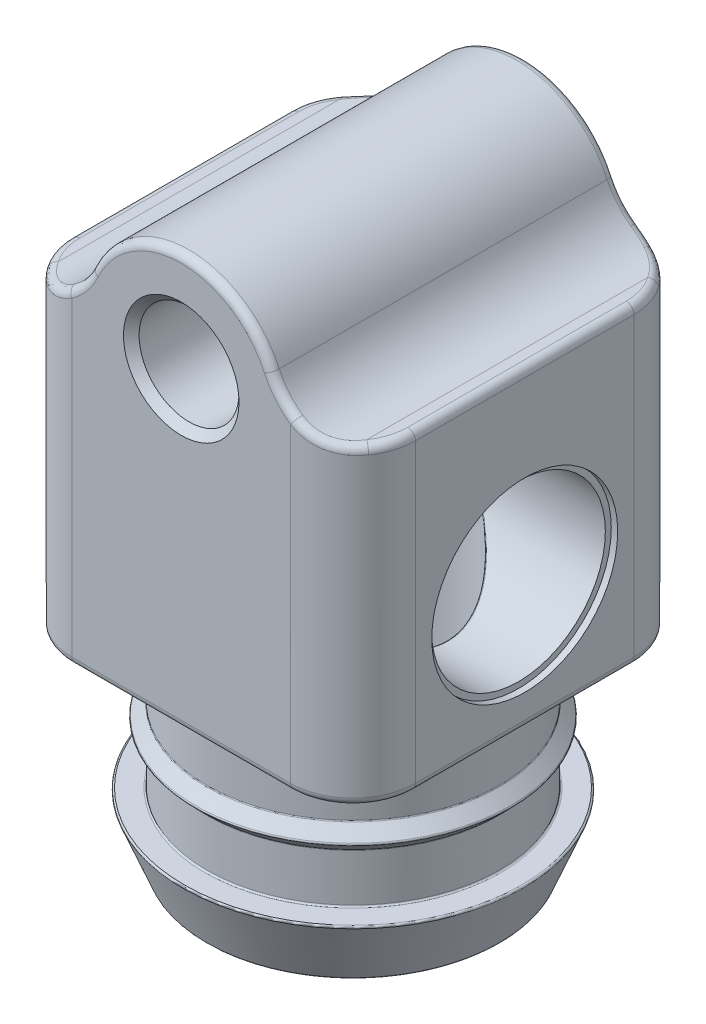
SolidWorks part; units mm, degrees
ref_plane "Front Plane" through (0, 0, 0) normal (0, 0, 1) x (1, 0, 0)
ref_plane "Top Plane" through (0, 0, 0) normal (0, 1, 0) x (1, 0, 0)
ref_plane "Right Plane" through (0, 0, 0) normal (1, 0, 0) x (0, 0, -1)
sketch "Sketch1" plane through (0, 0, 0) normal (0, 0, 1) x (1, 0, 0)
  line L3 (0, 0) -> (0, -20) construction
  line L4 (-11, 0) -> (-6.35, 0)
  line L5 (-11, 0) -> (-11, -20)
  line L6 (-11, -20) -> (11, -20)
  line L7 (11, 0) -> (11, -20)
  line L8 (6.35, 0) -> (11, 0)
  circle A0 centre (0, 0) radius 3.2
  arc A1 (6.35, 0) -> (-6.35, 0) centre (0, 0) ccw
  dimension "D1" = 6.4
  dimension "D2" = 12.7
  dimension "D4" = 22
  dimension "D5" = 20
extrude "Boss-Extrude1" add sketch "Sketch1" along normal mid plane 22
sketch3d "3DSketch1" plane through (0, 0, 0) normal (0, 0, 1) x (1, 0, 0)
  dimension "D1" = 12.7
sketch "Sketch2" plane through (0, 0, 0) normal (0, 0, 1) x (1, 0, 0)
  line L0 (0, 9.544) -> (0, -9.544) construction
  line L1 (0, -20) -> (9.365, -20)
  line L4 (0, -32.7) -> (9.365, -32.7)
  line L10 (0, -32.7) -> (0, -20)
  line L11 (9.365, -32.7) -> (10.9525, -28.7312)
  line L12 (10.9525, -28.7312) -> (9.365, -28.7312)
  line L13 (9.365, -28.7312) -> (9.365, -25.5562)
  line L14 (9.365, -25.5562) -> (10.1588, -24.7625)
  line L15 (10.1588, -24.7625) -> (9.365, -23.9687)
  line L16 (10.1588, -24.7625) -> (9.365, -24.7625) construction
  line L17 (9.365, -23.9687) -> (9.365, -20)
  dimension "D1" = 18.73
  dimension "D2" = 12.7
  dimension "D3" = 1.5875
  dimension "D4" = 3.9688
  dimension "D5" = 0.7937
  dimension "D6" = 7.9375
  dimension "D7" = 20
revolve "Revolve1" add sketch "Sketch2" angle 360 about L0
sketch "Sketch3" plane through (0, -32.7, 0) normal (0, -1, 0) x (1, 0, 0)
  circle A0 centre (0, 0) radius 6
  dimension "D1" = 12
extrude "Cut-Extrude1" cut sketch "Sketch3" against normal blind 27.25 contours A0
hole_wizard "1/4 NPT Tapped Hole1" positions "Sketch4" profile "Sketch5" size "1/4" standard "ANSI Inch" end condition up to next
sketch "Sketch4" plane through (11, 0, 0) normal (1, 0, 0) x (0, 0, -1)
  point P0 (0, -12)
  dimension "D1" = 12
cosmetic thread "Hole Thread1" parameters "D1"=0.4, "D2"=13.1394
sketch "Sketch5" plane through (11, -12, 0) normal (0, 1, 0) x (0, 0, -1)
  line L0 (0, 0) -> (0, 5)
  line L1 (0, 5) -> (5.5626, 5)
  line L2 (-5.9437, 0.4) -> (-5.9557, 0) construction
  line L3 (5.5626, 5) -> (5.5626, 0.4)
  line L4 (5.5626, 0.4) -> (5.9437, 0.4)
  line L5 (5.9437, 0.4) -> (5.9557, 0)
  line L7 (5.9557, 0) -> (0, 0)
  line L8 (0, -6.35) -> (0, 107.95) construction
  line L11 (-5.5626, 0.4) -> (-5.9437, 0.4) construction
  dimension "Thru Tap Drill Dia." = 11.1252
  dimension "Thru Tap Drill Depth" = 5
  dimension "Thread Dia." = 11.9113
  dimension "Thread Angle" = 3.43
  dimension "Thread Depth" = 0.4
fillet "Fillet3" radius 0.1 10 edges at (-10.9525, -28.7313, 0) (-10.1587, -24.7625, 0) (6, -32.7, 0) (6, -5.45, 0) (-9.365, -32.7, 0) (5.9593, -17.5187, -0.6973) (-9.365, -25.5562, 0) (-9.365, -23.9687, 0) (-9.365, -28.7313, 0) (-9.365, -20, 0)
chamfer "Chamfer1" distance 0.5 angle 45 2 edges at (3.2, 0, -11) (3.2, 0, 11)
fillet "Fillet7" radius 4.5 2 edges at (-6.35, 0, 0) (6.35, 0, 0)
fillet "Fillet6" radius 4 4 edges at (11, -10, -11) (-11, -10, -11) (-11, -10, 11) (11, -10, 11)
fillet "Fillet8" radius 0.5 24 edges at (-9.8284, -20, 9.8284) (-11, -20, 0) (-9.8284, -20, -9.8284) (0, -20, -11) (9.8284, -20, -9.8284) (11, -20, 0) (9.8284, -20, 9.8284) (10.7075, 0, 8.5015) (8.9278, 0.1004, 10.5048) (6.2987, 1.7659, 11) (0, 6.35, 11) (-6.2987, 1.7659, 11) (-8.0042, 0.4063, 10.8719) (-10.7075, 0, 8.5015) (-11, 0, 0) (-10.7075, 0, -8.5015) (-8.9278, 0.1004, -10.5048) (-6.2987, 1.7659, -11) (0, 6.35, -11) (6.2987, 1.7659, -11) (8.0042, 0.4063, -10.8719) (10.7075, 0, -8.5015) (0, -20, 11) (11, 0, 0)
